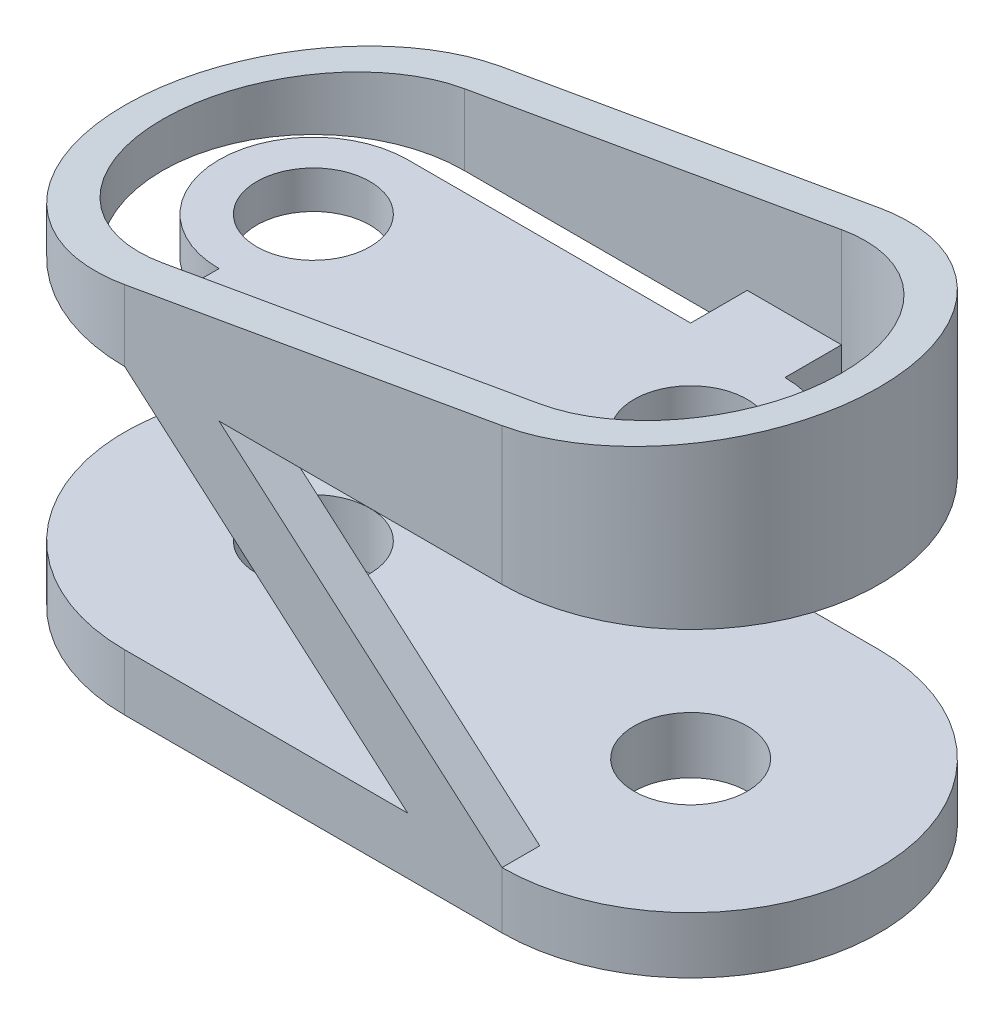
SolidWorks part; units mm, degrees
material "NBR"
ref_plane "Front Plane" through (0, 0, 0) normal (0, 0, 1) x (1, 0, 0)
ref_plane "Top Plane" through (0, 0, 0) normal (0, 1, 0) x (1, 0, 0)
ref_plane "Right Plane" through (0, 0, 0) normal (1, 0, 0) x (0, 0, -1)
sketch "Sketch1" plane through (0, 0, 0) normal (0, 1, 0) x (1, 0, 0)
  line L0 (-50, 0) -> (50, 0) construction
  line L1 (-50, 50) -> (50, 50)
  line L2 (50, -50) -> (-50, -50)
  line L3 (-50, 25) -> (25, 25)
  line L4 (50, -25) -> (-25, -25)
  line L5 (50, 25) -> (50, 50)
  line L6 (25, 50) -> (25, 25)
  line L7 (-50, -50) -> (-25, -50)
  line L8 (-50, -25) -> (-50, -50)
  line L9 (-25, -50) -> (-25, -25)
  arc A0 (-50, 50) -> (-50, -50) centre (-50, 0) ccw
  arc A1 (50, -50) -> (50, 50) centre (50, 0) ccw
  arc A4 (-50, 25) -> (-50, -25) centre (-50, 0) ccw
  arc A5 (50, -25) -> (50, 25) centre (50, 0) ccw
  circle A6 centre (-50, 0) radius 15
  circle A7 centre (50, 0) radius 15
  dimension "D2" = 100
  dimension "D3" = 25
  dimension "D4" = 50
  dimension "D6" = 30
  dimension "D1" = 100
  dimension "D5" = 25
extrude "Boss-Extrude1" add sketch "Sketch1" along normal blind 10 from offset 80 contours L4 A5 L5 L1 L6 L3 A4 L8 L2 L9 A6 A7 region at (0, 0, 0)
extrude "Boss-Extrude2" add sketch "Sketch1<3>" along normal blind 15 separate body contours A4 L3 L6 L1 A0 L8 | A5 L4 L9 L2 A1 L5 | L4 A5 L5 L1 L6 L3 A4 L8 L2 L9 A6 A7 region at (-12.5, 0, -48.3992) region at (0, 0, 0) region at (98.3992, 0, 0)
sketch "Sketch1<3>" plane through (0, 0, 0) normal (0, 1, 0) x (1, 0, 0) same geometry as "Sketch1"
sketch "Sketch2" plane through (0, 0, 50) normal (0, 0, 1) x (1, 0, 0)
  line L0 (50, 15) -> (-25, 80)
  line L1 (-25, 80) -> (-50, 80)
  line L2 (-50, 80) -> (25, 15)
  line L3 (50, 15) -> (-50, 15) construction
  line L4 (25, 15) -> (50, 15)
  dimension "D1" = 25
extrude "Boss-Extrude3" add sketch "Sketch2" against normal blind 10
sketch "Sketch3" plane through (0, 0, -50) normal (0, 0, -1) x (-1, 0, 0)
  line L0 (-25, 80) -> (50, 15)
  line L1 (50, 15) -> (25, 15)
  line L2 (50, 15) -> (-50, 15) construction
  line L3 (25, 15) -> (-50, 80)
  line L4 (-50, 80) -> (-25, 80)
extrude "Boss-Extrude4" add sketch "Sketch3" against normal blind 10
sketch "Sketch4" plane through (0, 90, 0) normal (0, 1, 0) x (1, 0, 0)
  line L0 (25, -50) -> (-50, -50) construction
  line L1 (-25, 50) -> (50, 50) construction
  line L2 (50, -50) -> (-50, -50)
  line L3 (-50, 50) -> (50, 50)
  line L4 (50, -40) -> (-50, -40)
  line L5 (-50, 40) -> (50, 40)
  line L8 (-25, -25) -> (50, -25)
  line L9 (50, 25) -> (50, 50)
  line L10 (50, 50) -> (25, 50)
  line L11 (25, 50) -> (25, 25)
  line L12 (25, 25) -> (-50, 25)
  line L13 (-50, -25) -> (-50, -50)
  line L14 (-50, -50) -> (-25, -50)
  line L15 (-25, -50) -> (-25, -25)
  line L18 (50, 50) -> (25, 50)
  line L22 (-50, -50) -> (-25, -50)
  arc A0 (50, -50) -> (50, 50) centre (50, 0) ccw construction
  arc A1 (-50, 50) -> (-50, -50) centre (-50, 0) ccw construction
  arc A2 (50, -25) -> (50, 25) centre (50, 0) ccw
  arc A3 (-50, 25) -> (-50, -25) centre (-50, 0) ccw
  arc A6 (50, -50) -> (50, 50) centre (50, 0) ccw
  arc A7 (-50, 50) -> (-50, -50) centre (-50, 0) ccw
  arc A8 (-50, 40) -> (-50, -40) centre (-50, 0) ccw
  arc A9 (50, -40) -> (50, 40) centre (50, 0) ccw
  line M15 (50, 25) -> (50, 50)
  line M16 (50, 50) -> (25, 50)
  line M17 (25, 50) -> (25, 25)
  line M20 (-50, -25) -> (-50, -50)
  line M21 (-50, -50) -> (-25, -50)
  line M22 (-25, -50) -> (-25, -25)
  dimension "D1" = 0
  dimension "D2" = 10
extrude "Boss-Extrude6" add sketch "Sketch4" along normal blind 60 contours A9 L4 L2 A6 M22 M15 | L5 M17 M15 M16 | A8 L5 L3 A7 M17 M20 | L4 M22 M20 M21 region at (12.5, 90, 48.3992) region at (-37.5, 90, 45) region at (37.5, 90, -45) region at (-98.3992, 90, 0)
sketch "Sketch5" plane through (0, 90, 0) normal (0, 1, 0) x (1, 0, 0)
  line L0 (0, 0) -> (-100, 0) construction
  arc A0 (-50, 50) -> (-50, -50) centre (-50, 0) ccw construction
sketch "Sketch6" plane through (0, 0, 0) normal (0, 0, 1) x (1, 0, 0)
  line L0 (-100, 90) -> (134.6692, 131.3785)
  line L1 (0, 90) -> (-100, 90) construction
  dimension "D1" = 10
extrude "Cut-Extrude1" cut sketch "Sketch6" against normal through all both and the other way through all
sketch "Sketch7" plane through (0, 90, 0) normal (0, -1, 0) x (1, 0, 0)
  line L1 (-50, -40) -> (50, -40)
  line L2 (25, -50) -> (-50, -50) construction
  line L3 (50, -50) -> (-50, -50)
  line L4 (50, -40) -> (50, -50)
  line L5 (50, 50) -> (-25, 50)
  line L6 (-25, 50) -> (-25, 40)
  line L7 (-25, 40) -> (50, 40)
  line L9 (50, 50) -> (-27.6841, 50)
  line L11 (-50, 40) -> (50, 40)
  line L14 (-27.6841, 50) -> (-50, 50)
  arc A0 (-50, 40) -> (-50, -40) centre (-50, 0) ccw construction
  arc A1 (-50, 40) -> (-50, -40) centre (-50, 0) ccw
  arc A2 (50, -40) -> (50, 40) centre (50, 0) ccw
  arc A3 (50, -50) -> (50, 50) centre (50, 0) ccw
  arc A4 (50, -40) -> (50, 40) centre (50, 0) ccw
  arc A5 (50, -50) -> (50, 50) centre (50, 0) ccw
  arc A6 (-100, 0) -> (-50, -50) centre (-50, 0) ccw construction
  arc A7 (-50, 50) -> (-100, 0) centre (-50, 0) ccw construction
  arc A8 (-100, 0) -> (-50, -50) centre (-50, 0) ccw
  arc A9 (-50, 50) -> (-100, 0) centre (-50, 0) ccw
  dimension "D1" = 0
extrude "Boss-Extrude7" add sketch "Sketch7" along normal blind 10
